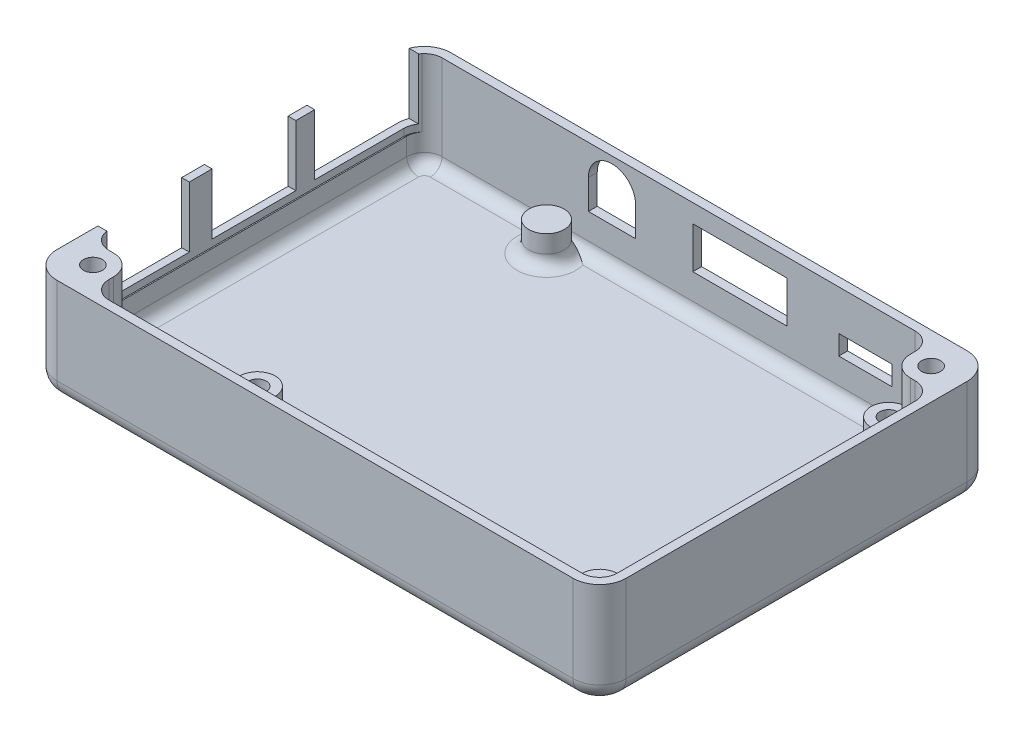
SolidWorks part; units mm, degrees
note: The reader was unsure of these and kept them because the rebuilt part matched: shared geometry of "Sketch1<3>", "Sketch6<2>".
ref_plane "Front Plane" through (0, 0, 0) normal (0, 0, 1) x (1, 0, 0)
ref_plane "Top Plane" through (0, 0, 0) normal (0, 1, 0) x (1, 0, 0)
ref_plane "Right Plane" through (0, 0, 0) normal (1, 0, 0) x (0, 0, -1)
sketch "Sketch1" plane through (0, 0, 0) normal (0, 1, 0) x (1, 0, 0)
  line L0 (-54.9012, 31.4676) -> (32.5988, 31.4676)
  line L1 (-54.9012, -33.8324) -> (32.5988, -33.8324)
  line L2 (-57.9012, -30.8324) -> (-57.9012, 26.9676)
  line L3 (-54.9012, 29.9676) -> (32.5988, 29.9676)
  line L4 (35.5988, -30.8324) -> (35.5988, 26.9676)
  line L5 (-57.9012, -33.8324) -> (35.5988, 29.9676) construction
  line L6 (-57.9012, 29.9676) -> (35.5988, -33.8324) construction
  line L7 (37.0988, -30.8324) -> (37.0988, 26.9676)
  line L8 (-54.9012, -35.3324) -> (32.5988, -35.3324)
  line L9 (-59.4012, -30.8324) -> (-59.4012, 26.9676)
  line L10 (27.5988, -22.8324) -> (27.5988, 27.0676) construction
  line L11 (-54.4012, -25.8324) -> (24.5988, -25.8324) construction
  line L16 (24.5988, 30.0676) -> (20.8488, 30.0676) construction
  line L17 (-57.4012, -5.3324) -> (-57.4012, -10.1824) construction
  arc A0 (32.5988, 29.9676) -> (35.5988, 26.9676) centre (32.5988, 26.9676) cw
  arc A1 (32.5988, -33.8324) -> (35.5988, -30.8324) centre (32.5988, -30.8324) ccw
  arc A2 (-54.9012, -33.8324) -> (-57.9012, -30.8324) centre (-54.9012, -30.8324) cw
  arc A3 (-57.9012, 26.9676) -> (-54.9012, 29.9676) centre (-54.9012, 26.9676) cw
  arc A4 (32.5988, 31.4676) -> (37.0988, 26.9676) centre (32.5988, 26.9676) cw
  arc A5 (32.5988, -35.3324) -> (37.0988, -30.8324) centre (32.5988, -30.8324) ccw
  arc A6 (-54.9012, -35.3324) -> (-59.4012, -30.8324) centre (-54.9012, -30.8324) cw
  arc A7 (-59.4012, 26.9676) -> (-54.9012, 31.4676) centre (-54.9012, 26.9676) cw
  point P0 (0, 0)
  dimension "D1" = 3
  dimension "D3" = 8
  dimension "D4" = 8
  dimension "D5" = 0.1
  dimension "D6" = 0.5
  dimension "D2" = 1.5
extrude "Boss-Extrude1" add sketch "Sketch1" along normal blind 1.25 contours L2 A3 L3 A0 L4 A1 L1 A2
extrude "Boss-Extrude2" add sketch "Sketch1<3>" along normal up to surface (17.75 mm away)
sketch "Sketch1<3>" plane through (0, 0, 0) normal (0, 1, 0) x (1, 0, 0) same geometry as "Sketch1"
sketch "Sketch2" plane through (0, 17.75, 0) normal (0, 1, 0) x (1, 0, 0)
  line L0 (27.7988, -25.6324) -> (27.7988, 26.6676)
  line L1 (24.5988, 29.8676) -> (-54.9012, 29.8676)
  line L2 (-58.1012, 26.6676) -> (-58.1012, -22.4324)
  line L3 (-54.9012, -25.6324) -> (27.7988, -25.6324)
  line L4 (24.5988, 30.0676) -> (20.8488, 30.0676) construction
  line L5 (27.5988, 7.6176) -> (27.5988, 27.0676) construction
  line L6 (24.5988, 29.8676) -> (24.5988, 30.0676) construction
  line L7 (-57.9012, 26.9676) -> (-57.9012, -30.8324) construction
  line L8 (-54.4012, -25.8324) -> (24.5988, -25.8324) construction
  arc A0 (27.7988, 26.6676) -> (24.5988, 29.8676) centre (24.5988, 26.6676) ccw
  arc A1 (-54.9012, 29.8676) -> (-58.1012, 26.6676) centre (-54.9012, 26.6676) ccw
  arc A2 (-58.1012, -22.4324) -> (-54.9012, -25.6324) centre (-54.9012, -22.4324) ccw
  dimension "D1" = 0.2
  dimension "D2" = 0.2
  dimension "D3" = 0.2
  dimension "D4" = 0.2
extrude "Cut-Extrude1" cut sketch "Sketch2" against normal up to vertex (11.5 mm away)
sketch "Sketch3" plane through (0, 1.25, 0) normal (0, 1, 0) x (1, 0, 0)
  circle A0 centre (24.1488, -22.3824) radius 3
  circle A1 centre (-33.8512, -22.3824) radius 3
  circle A2 centre (24.1488, 26.6176) radius 3
  circle A3 centre (-33.8512, 26.6176) radius 3
  circle A4 centre (-33.8512, -22.3824) radius 1.5
  circle A5 centre (24.1488, 26.6176) radius 1.5
  circle A6 centre (24.1488, -22.3824) radius 1.5 construction
  circle A7 centre (24.1488, 26.6176) radius 1.5 construction
  circle A8 centre (-33.8512, 26.6176) radius 1.5 construction
  circle A9 centre (-33.8512, -22.3824) radius 1.5 construction
  dimension "D1" = 3
  dimension "D2" = 1.5
extrude "Boss-Extrude3" add sketch "Sketch3" along normal up to surface (5 mm away)
sketch "Sketch4" plane through (0, 0, -31.4676) normal (0, 0, -1) x (-1, 0, 0)
  line L0 (-12.8488, 7.75) -> (-20.8488, 7.75) construction
  line L1 (-21.3488, 7.6) -> (-12.3488, 7.6)
  line L2 (-21.3488, 7.6) -> (-21.3488, 10.91)
  line L3 (-21.3488, 10.91) -> (-12.3488, 10.91)
  line L4 (-12.3488, 7.6) -> (-12.3488, 10.91)
  line L5 (-3.5988, 7.6) -> (12.4012, 7.6)
  line L6 (-3.5988, 7.6) -> (-3.5988, 14.65)
  line L7 (-3.5988, 14.65) -> (12.4012, 14.65)
  line L8 (12.4012, 7.6) -> (12.4012, 14.65)
  line L9 (22.1012, 7.6) -> (30.1012, 7.6)
  line L10 (22.1012, 7.6) -> (22.1012, 12.6)
  line L12 (30.1012, 7.6) -> (30.1012, 12.6)
  line L13 (-20.8488, 10.41) -> (-20.8488, 7.75) construction
  line L14 (-12.8488, 10.41) -> (-12.8488, 7.75) construction
  line L15 (-12.8488, 10.41) -> (-20.8488, 10.41) construction
  line L16 (-3.0988, 13.85) -> (-3.0988, 7.75) construction
  line L17 (11.9012, 13.85) -> (11.9012, 7.75) construction
  line L18 (-3.0988, 13.85) -> (11.9012, 13.85) construction
  line L19 (22.6012, 13.35) -> (22.6012, 7.75) construction
  line L20 (29.6012, 13.35) -> (29.6012, 7.75) construction
  arc A0 (22.1012, 12.6) -> (30.1012, 12.6) centre (26.1012, 12.6) cw
  dimension "D1" = 0.15
  dimension "D2" = 0.5
  dimension "D3" = 0.5
  dimension "D4" = 0.5
  dimension "D5" = 0.5
  dimension "D6" = 0.5
  dimension "D7" = 0.8
  dimension "D8" = 0.5
  dimension "D9" = 0.5
  dimension "D10" = 5
extrude "Cut-Extrude2" cut sketch "Sketch4" against normal up to next
sketch "Sketch5" plane through (-59.4012, 0, 0) normal (-1, 0, 0) x (0, 0, 1)
  line L0 (30.8324, 17.75) -> (-26.9676, 17.75) construction
  line L1 (-28.5676, 17.75) -> (-11.5676, 17.75)
  line L2 (-28.5676, 17.75) -> (-28.5676, 7.45)
  line L3 (-28.5676, 7.45) -> (-11.5676, 7.45)
  line L4 (-11.5676, 17.75) -> (-11.5676, 7.45)
  line L5 (-8.3676, 17.75) -> (5.8324, 17.75)
  line L6 (-8.3676, 17.75) -> (-8.3676, 7.45)
  line L7 (-8.3676, 7.45) -> (5.8324, 7.45)
  line L8 (5.8324, 17.75) -> (5.8324, 7.45)
  line L9 (-28.0676, 21.75) -> (-28.0676, 7.75) construction
  line L10 (9.6824, 17.75) -> (23.8824, 17.75)
  line L11 (9.6824, 17.75) -> (9.6824, 7.45)
  line L12 (9.6824, 7.45) -> (23.8824, 7.45)
  line L13 (23.8824, 17.75) -> (23.8824, 7.45)
  line L14 (-28.0676, 7.75) -> (-12.0676, 7.75) construction
  line L15 (-12.0676, 21.75) -> (-12.0676, 7.75) construction
  line L16 (-7.8676, 23.25) -> (-7.8676, 7.75) construction
  line L17 (5.3324, 23.25) -> (5.3324, 7.75) construction
  line L18 (10.1824, 23.25) -> (10.1824, 7.75) construction
  line L19 (23.3824, 23.25) -> (23.3824, 7.75) construction
  dimension "D1" = 0.5
  dimension "D2" = 0.3
  dimension "D3" = 0.5
  dimension "D4" = 0.5
  dimension "D5" = 0.5
  dimension "D6" = 0.5
  dimension "D7" = 0.5
extrude "Cut-Extrude3" cut sketch "Sketch5" against normal up to next
sketch "Sketch6" plane through (0, 0, 0) normal (0, 1, 0) x (1, 0, 0)
  line L0 (37.0988, 26.1682) -> (31.7994, 26.1682) construction
  line L2 (31.7994, 26.1682) -> (31.7994, 31.4676) construction
  line L4 (-59.4012, -30.033) -> (-54.1018, -30.033) construction
  line L5 (-54.1018, -30.033) -> (-54.1018, -35.3324) construction
  line L8 (32.5988, 31.4676) -> (-54.9012, 31.4676) construction
  line L9 (37.0988, -30.8324) -> (37.0988, 26.9676) construction
  line L10 (-54.9012, -35.3324) -> (32.5988, -35.3324) construction
  line L11 (-59.4012, 26.9676) -> (-59.4012, -30.8324) construction
  circle A0 centre (31.7994, 26.1682) radius 2.5
  circle A1 centre (31.7994, 26.1682) radius 1.6
  circle A2 centre (-54.1018, -30.033) radius 2.5
  circle A3 centre (-54.1018, -30.033) radius 1.6
  dimension "D1" = 3.2
  dimension "D2" = 5
sketch "Sketch7" plane through (0, 1.25, 0) normal (0, 1, 0) x (1, 0, 0)
  line L0 (31.7994, 22.6682) -> (35.5988, 22.6682)
  line L1 (35.5988, 22.6682) -> (35.5988, 26.9676)
  line L2 (32.5988, 29.9676) -> (28.2994, 29.9676)
  line L3 (-54.9012, 29.9676) -> (32.5988, 29.9676) construction
  line L4 (28.2994, 29.9676) -> (28.2994, 26.1682)
  line L5 (35.5988, -30.8324) -> (35.5988, 26.9676) construction
  line L6 (-50.6018, -30.033) -> (-50.6018, -33.8324)
  line L7 (-54.9012, -33.8324) -> (32.5988, -33.8324) construction
  line L8 (-50.6018, -33.8324) -> (-54.9012, -33.8324)
  line L9 (-57.9012, -30.8324) -> (-57.9012, -26.533)
  line L10 (-57.9012, -30.8324) -> (-57.9012, 26.9676) construction
  line L11 (-57.9012, -26.533) -> (-54.1018, -26.533)
  arc A0 (31.7994, 22.6682) -> (28.2994, 26.1682) centre (31.7994, 26.1682) cw
  arc A1 (-50.6018, -30.033) -> (-54.1018, -26.533) centre (-54.1018, -30.033) ccw
  arc A2 (35.5988, 26.9676) -> (32.5988, 29.9676) centre (32.5988, 26.9676) ccw
  arc A4 (-54.9012, -33.8324) -> (-57.9012, -30.8324) centre (-54.9012, -30.8324) cw
  point P21 (28.2028, 26.1682)
  dimension "D1" = 3.5
extrude "Boss-Extrude4" add sketch "Sketch7" along normal up to surface (16.5 mm away) up to face at (-18.4861, 17.75, 2.4861)
extrude "Cut-Extrude4" cut sketch "Sketch6" along normal blind 3
extrude "Cut-Extrude5" cut sketch "Sketch6<2>" along normal through all contours A1 | A3
sketch "Sketch6<2>" plane through (0, 0, 0) normal (0, 1, 0) x (1, 0, 0) same geometry as "Sketch6"
fillet "Fillet4" radius 3 4 edges at (-50.6018, 9.5, 33.8324) (35.5988, 9.5, -22.6682) (-57.9012, 9.5, 26.533) (28.2994, 9.5, -29.9676)
fillet "Fillet1" radius 3 8 edges at (-58.0832, 0, 34.0144) (-59.4012, 0, 1.9324) (-58.0832, 0, -30.1495) (-11.1512, 0, -31.4676) (35.7808, 0, -30.1495) (37.0988, 0, 1.9324) (35.7808, 0, 34.0144) (-11.1512, 0, 35.3324)
fillet "Fillet2" radius 2 20 edges at (35.5988, 1.25, 5.5821) (-7.5015, 1.25, 33.8324) (-57.9012, 1.25, -1.7173) (-57.0225, 1.25, -29.0889) (-14.8009, 1.25, -29.9676) (34.7201, 1.25, 32.9538) (24.1488, 1.25, 19.3824) (-33.8512, 1.25, 19.3824) (24.1488, 1.25, -29.6176) (-33.8512, 1.25, -29.6176) (-51.627, 1.25, 27.5582) (-54.5015, 1.25, 26.533) (29.3245, 1.25, -23.6933) (32.1991, 1.25, -22.6682) (-50.6018, 1.25, 30.4327) (34.7201, 1.25, -21.7895) (-49.7232, 1.25, 32.9538) (28.2994, 1.25, -26.5679) (27.4207, 1.25, -29.0889) (-57.0225, 1.25, 25.6544)
